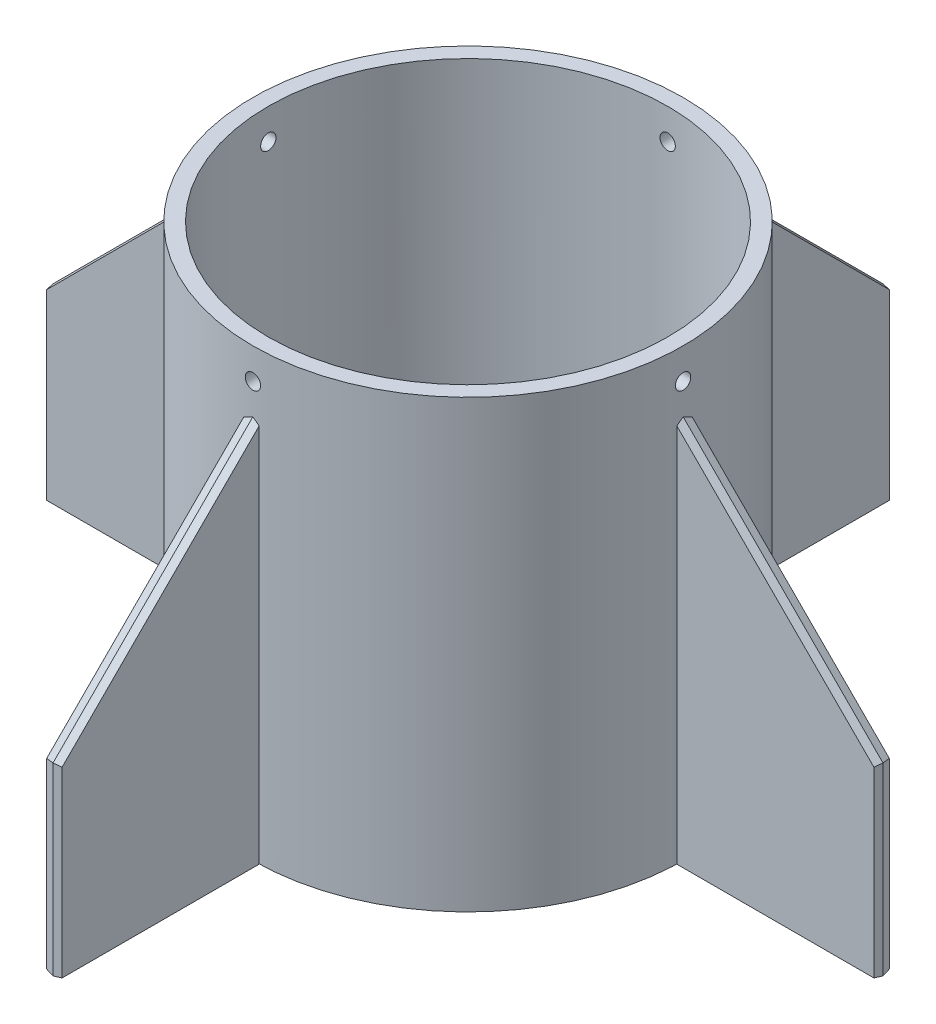
SolidWorks part; units mm, degrees
ref_plane "Front Plane" through (0, 0, 0) normal (0, 0, 1) x (1, 0, 0)
ref_plane "Top Plane" through (0, 0, 0) normal (0, 1, 0) x (1, 0, 0)
ref_plane "Right Plane" through (0, 0, 0) normal (1, 0, 0) x (0, 0, -1)
sketch "Sketch1" plane through (0, 0, 0) normal (0, 1, 0) x (1, 0, 0)
  circle A0 centre (0, 0) radius 88.9
  circle A1 centre (0, 0) radius 82.55
  dimension "D1" = 177.8
extrude "Base Shell" add sketch "Sketch1" along normal blind 184.15
sketch "Sketch2" plane through (0, 0, 0) normal (0, 1, 0) x (1, 0, 0)
  line L0 (0, -82.55) -> (0, 82.55) construction
  line L1 (-82.55, 0) -> (82.55, 0) construction
  line L2 (-69.85, 0) -> (-76.2, 0) construction
  line L3 (-82.3054, -6.35) -> (-72.39, -6.35)
  line L5 (-82.3054, 6.35) -> (-72.39, 6.35)
  line L6 (-69.85, -3.81) -> (-69.85, 3.81)
  line L7 (-82.55, 0) -> (-69.85, 6.35) construction
  line L8 (-82.55, 0) -> (-69.85, -6.35) construction
  line L9 (6.35, 82.3054) -> (6.35, 72.39)
  line L10 (-6.35, 82.3054) -> (-6.35, 72.39)
  line L11 (-3.81, 69.85) -> (3.81, 69.85)
  line L12 (82.3054, -6.35) -> (72.39, -6.35)
  line L13 (82.3054, 6.35) -> (72.39, 6.35)
  line L14 (69.85, 3.81) -> (69.85, -3.81)
  line L15 (-6.35, -82.3054) -> (-6.35, -72.39)
  line L16 (6.35, -82.3054) -> (6.35, -72.39)
  line L17 (3.81, -69.85) -> (-3.81, -69.85)
  circle A0 centre (0, 0) radius 82.55 construction
  circle A1 centre (-76.2, 0) radius 3.175
  arc A2 (-72.39, -6.35) -> (-69.85, -3.81) centre (-72.39, -3.81) ccw
  arc A3 (-69.85, 3.81) -> (-72.39, 6.35) centre (-72.39, 3.81) ccw
  arc A4 (-82.3054, 6.35) -> (-82.3054, -6.35) centre (0, 0) ccw
  arc A5 (6.35, 82.3054) -> (-6.35, 82.3054) centre (0, 0) ccw
  circle A6 centre (0, 76.2) radius 3.175
  arc A7 (-6.35, 72.39) -> (-3.81, 69.85) centre (-3.81, 72.39) ccw
  arc A8 (3.81, 69.85) -> (6.35, 72.39) centre (3.81, 72.39) ccw
  arc A9 (82.3054, -6.35) -> (82.3054, 6.35) centre (0, 0) ccw
  circle A10 centre (76.2, 0) radius 3.175
  arc A11 (72.39, 6.35) -> (69.85, 3.81) centre (72.39, 3.81) ccw
  arc A12 (69.85, -3.81) -> (72.39, -6.35) centre (72.39, -3.81) ccw
  arc A13 (-6.35, -82.3054) -> (6.35, -82.3054) centre (0, 0) ccw
  circle A14 centre (0, -76.2) radius 3.175
  arc A15 (6.35, -72.39) -> (3.81, -69.85) centre (3.81, -72.39) ccw
  arc A16 (-3.81, -69.85) -> (-6.35, -72.39) centre (-3.81, -72.39) ccw
  point P55 (0, 0)
  dimension "D4" = 2.54
  dimension "D1" = 4
  dimension "D3" = 6.35
extrude "Bolt Tabs" add sketch "Sketch2" along normal blind 3.175
sketch "Sketch3" plane through (0, 0, 0) normal (0, 0, 1) x (1, 0, 0)
  line L0 (0, 0) -> (0, 184.15) construction
  line L1 (82.55, 184.15) -> (-82.55, 184.15) construction
  line L2 (-88.9, 0) -> (-171.45, 0)
  line L3 (-171.45, 0) -> (-171.45, 76.2)
  line L4 (-171.45, 76.2) -> (-88.9, 158.75)
  line L5 (-88.9, 184.15) -> (-88.9, 0) construction
  line L6 (-88.9, 158.75) -> (-88.9, 0)
  line L7 (171.45, 76.2) -> (88.9, 158.75)
  line L8 (171.45, 0) -> (171.45, 76.2)
  line L9 (88.9, 0) -> (171.45, 0)
  line L10 (88.9, 158.75) -> (88.9, 0)
  line L11 (-88.9, 158.75) -> (88.9, 158.75) construction
  line L12 (0, 184.15) -> (0, 158.75) construction
  point P19 (0, 184.15)
  dimension "D1" = 82.55
  dimension "D2" = 76.2
  dimension "D3" = 45
extrude "Fins1" add sketch "Sketch3" along normal mid plane 6.35 draft 10 separate body
sketch "Sketch4" plane through (0, 0, 0) normal (1, 0, 0) x (0, 0, -1)
  line L0 (0, 0) -> (0, 184.15) construction
  line L1 (82.55, 184.15) -> (-82.55, 184.15) construction
  line L2 (-88.9, 0) -> (-171.45, 0)
  line L3 (-171.45, 0) -> (-171.45, 76.2)
  line L4 (-171.45, 76.2) -> (-88.9, 158.75)
  line L5 (-88.9, 184.15) -> (-88.9, 0) construction
  line L6 (-88.9, 158.75) -> (-88.9, 0)
  line L7 (171.45, 76.2) -> (88.9, 158.75)
  line L8 (171.45, 0) -> (171.45, 76.2)
  line L9 (88.9, 0) -> (171.45, 0)
  line L10 (88.9, 158.75) -> (88.9, 0)
  dimension "D1" = 82.55
  dimension "D2" = 76.2
  dimension "D3" = 45
extrude "Fins2" add sketch "Sketch4" along normal mid plane 6.35 draft 10 separate body
sketch "Sketch5" plane through (0, 0, 0) normal (0, 0, 1) x (1, 0, 0)
  line L0 (0, 184.15) -> (0, 158.75) construction
  line L1 (82.55, 184.15) -> (-82.55, 184.15) construction
  circle A0 centre (0, 171.45) radius 3.175
extrude "Cut-Extrude1" cut sketch "Sketch5" against normal through all both and the other way through all
sketch "Sketch6" plane through (0, 0, 0) normal (1, 0, 0) x (0, 0, -1)
  line L0 (0, 184.15) -> (0, 158.75) construction
  line L1 (88.9, 184.15) -> (-88.9, 184.15) construction
  circle A0 centre (0, 171.45) radius 3.175
extrude "Cut-Extrude2" cut sketch "Sketch6" against normal through all both and the other way through all
